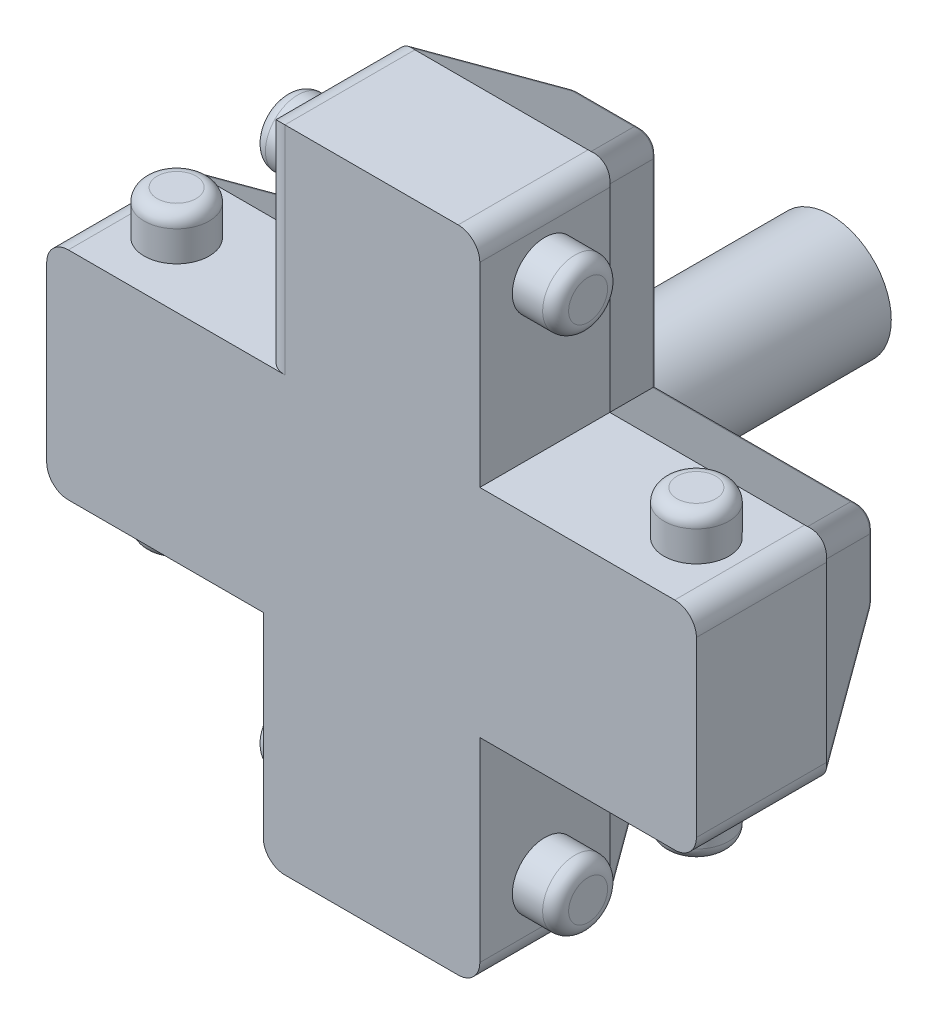
SolidWorks part; units mm, degrees
ref_plane "Front Plane" through (0, 0, 0) normal (0, 0, 1) x (1, 0, 0)
ref_plane "Top Plane" through (0, 0, 0) normal (0, 1, 0) x (1, 0, 0)
ref_plane "Right Plane" through (0, 0, 0) normal (1, 0, 0) x (0, 0, -1)
sketch "Sketch1" plane through (0, 0, 0) normal (0, 0, 1) x (1, 0, 0)
  circle A0 centre (0, 0) radius 14
  dimension "D1" = 28
extrude "Boss-Extrude1" add sketch "Sketch1" along normal blind 76
sketch "Sketch3" plane through (0, 0, 76) normal (0, 0, 1) x (1, 0, 0)
  line L1 (-75, 25) -> (75, 25)
  line L2 (-75, 25) -> (-75, -25)
  line L3 (-75, -25) -> (75, -25)
  line L4 (75, 25) -> (75, -25)
  line L5 (-75, 25) -> (75, -25) construction
  line L6 (-75, -25) -> (75, 25) construction
  line L7 (-25, 75) -> (25, 75)
  line L8 (-25, 75) -> (-25, -75)
  line L9 (-25, -75) -> (25, -75)
  line L10 (25, 75) -> (25, -75)
  line L11 (-25, 75) -> (25, -75) construction
  line L12 (-25, -75) -> (25, 75) construction
  point P0 (0, 0)
  point P6 (0, 0)
  circle M5 centre (0, 0) radius 14
  dimension "D1" = 150
  dimension "D2" = 150
  dimension "D3" = 50
  dimension "D4" = 50
extrude "Boss-Extrude2" add sketch "Sketch3" along normal blind 30 separate body contours L10 L3 L8 L9 | L8 L1 L2 L3 | L10 L1 L8 L3 M5 | L1 L10 L3 L4 | L10 L7 L8 L1 | M5
ref_plane "Plane1" through (0, 0, 0) normal (-1, 0, 0) x (0, 0, 1)
sketch "Sketch4" plane through (0, 0, 0) normal (-1, 0, 0) x (0, 0, 1)
  line L0 (91, 75) -> (91, 25) construction
  line L1 (106, 75) -> (76, 75) construction
  line L2 (106, 25) -> (76, 25) construction
  line L3 (0, 0) -> (76, 0) construction
  line L4 (76, -14) -> (76, 14) construction
  line L5 (91, -75) -> (91, -25) construction
  circle A0 centre (91, 60) radius 7.5
  circle A1 centre (91, -60) radius 7.5
  dimension "D1" = 15
  dimension "D2" = 15
extrude "Boss-Extrude3" add sketch "Sketch4" along normal mid plane 70
sketch "Sketch5" plane through (0, 0, 0) normal (0, 1, 0) x (1, 0, 0)
  line L0 (-75, -91) -> (-25, -91) construction
  line L1 (-75, -106) -> (-75, -76) construction
  line L2 (-25, -83.5) -> (-25, -98.5) construction
  line L3 (0, 0) -> (0, -76) construction
  line L4 (-25, -76) -> (25, -76) construction
  line L5 (75, -91) -> (25, -91) construction
  circle A0 centre (-60, -91) radius 7.5
  circle A1 centre (60, -91) radius 7.5
  dimension "D1" = 15
  dimension "D2" = 15
extrude "Boss-Extrude4" add sketch "Sketch5" along normal mid plane 70
sketch "Sketch6" plane through (0, 0, 76) normal (0, 0, -1) x (-1, 0, 0)
  line L12 (-25, -25) -> (-25, -75)
  line L13 (-25, -75) -> (25, -75)
  line L14 (25, -75) -> (25, -25)
  line L15 (25, -25) -> (75, -25)
  line L16 (75, -25) -> (75, 25)
  line L17 (75, 25) -> (25, 25)
  line L18 (25, 25) -> (25, 75)
  line L19 (25, 75) -> (-25, 75)
  line L20 (-25, 75) -> (-25, 25)
  line L21 (-25, 25) -> (-75, 25)
  line L22 (-75, 25) -> (-75, -25)
  line L23 (-75, -25) -> (-25, -25)
  line L24 (-25, -25) -> (-25, -75)
  line L25 (-25, -75) -> (25, -75)
  line L26 (25, -75) -> (25, -25)
  line L27 (25, -25) -> (75, -25)
  line L28 (75, -25) -> (75, 25)
  line L29 (75, 25) -> (25, 25)
  line L30 (25, 25) -> (25, 75)
  line L31 (25, 75) -> (-25, 75)
  line L32 (-25, 75) -> (-25, 25)
  line L33 (-25, 25) -> (-75, 25)
  line L34 (-75, 25) -> (-75, -25)
  line L35 (-75, -25) -> (-25, -25)
  dimension "D1" = 0
extrude "Boss-Extrude5" add sketch "Sketch6" along normal blind 26 draft 30
fillet "Fillet1" radius 5 29 edges at (75, 25, 91) (25, 75, 91) (-25, 75, 91) (75, -25, 91) (-75, 25, 91) (-75, -25, 91) (-25, -75, 91) (-25, 50, 106) (25, -75, 91) (17.4944, -67.4944, 63) (-17.4944, -67.4944, 63) (-67.4944, -17.4944, 63) (-67.4944, 17.4944, 63) (-17.4944, 67.4944, 63) (17.4944, 67.4944, 63) (67.4944, -17.4944, 63) (67.4944, 17.4944, 63) (59.9889, 0, 50) (34.9889, 9.9889, 50) (0, 59.9889, 50) (-9.9889, 34.9889, 50) (-34.9889, 9.9889, 50) (-59.9889, 0, 50) (-34.9889, -9.9889, 50) (-9.9889, -34.9889, 50) (0, -59.9889, 50) (9.9889, -34.9889, 50) (34.9889, -9.9889, 50) (9.9889, 34.9889, 50)
fillet "Fillet2" radius 3 4 edges at (35, -52.5, 91) (35, 52.5, 91) (-35, 52.5, 91) (-35, -52.5, 91)
fillet "Fillet3" radius 3 4 edges at (60, 35, 83.5) (-60, -35, 98.5) (-60, 35, 98.5) (60, -35, 83.5)
